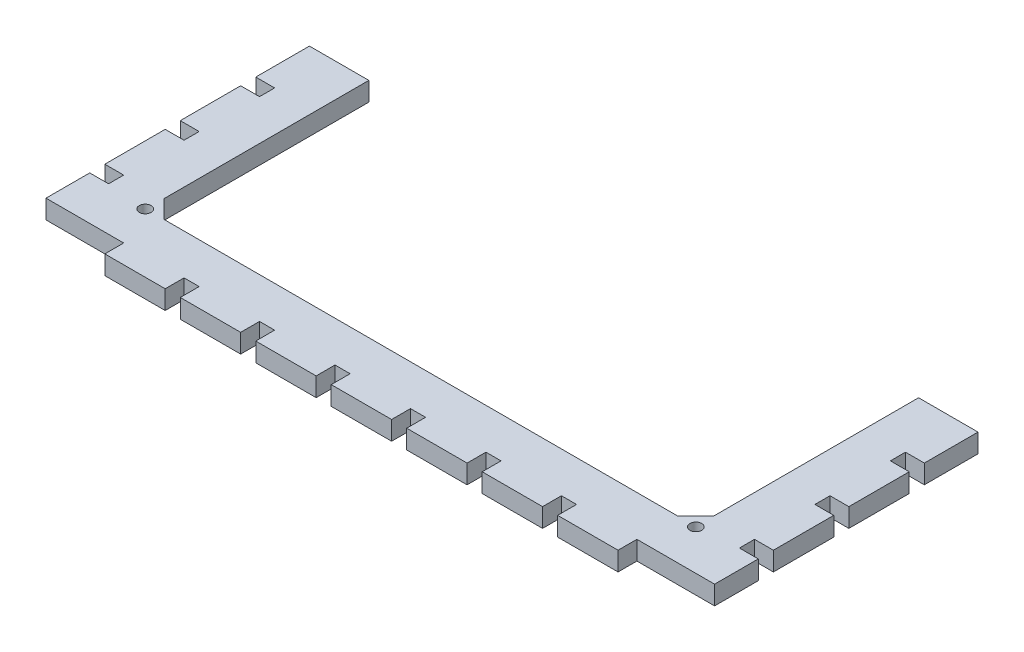
SolidWorks part; units mm, degrees
ref_plane "Front Plane" through (0, 0, 0) normal (0, 0, 1) x (1, 0, 0)
ref_plane "Top Plane" through (0, 0, 0) normal (0, 1, 0) x (1, 0, 0)
ref_plane "Right Plane" through (0, 0, 0) normal (1, 0, 0) x (0, 0, -1)
sketch "Sketch1" plane through (0, 0, 0) normal (0, 1, 0) x (1, 0, 0)
  line L48 (32.1429, 0) -> (32.1429, 6.35)
  line L49 (0, 0) -> (32.1429, 0)
  line L50 (0, 0) -> (0, 6.35)
  line L51 (0, 6.35) -> (32.1429, 6.35)
  line L52 (32.1429, 0) -> (32.1429, 6.35)
  line L53 (0, 0) -> (6.35, 0)
  line L54 (0, 0) -> (0, 32.1429)
  line L55 (0, 32.1429) -> (6.35, 32.1429)
  line L56 (6.35, 0) -> (6.35, 32.1429)
  line L57 (32.1429, 0) -> (64.2857, 0)
  line L58 (64.2857, 0) -> (64.2857, 6.35)
  line L59 (32.1429, 6.35) -> (64.2857, 6.35)
  line L60 (64.2857, 0) -> (64.2857, 6.35)
  line L61 (64.2857, 0) -> (96.4286, 0)
  line L62 (96.4286, 0) -> (96.4286, 6.35)
  line L63 (64.2857, 6.35) -> (96.4286, 6.35)
  line L64 (96.4286, 0) -> (96.4286, 6.35)
  line L65 (96.4286, 0) -> (128.5714, 0)
  line L66 (128.5714, 0) -> (128.5714, 6.35)
  line L67 (96.4286, 6.35) -> (128.5714, 6.35)
  line L72 (128.5714, 0) -> (128.5714, 6.35)
  line L73 (128.5714, 0) -> (160.7143, 0)
  line L74 (160.7143, 0) -> (160.7143, 6.35)
  line L75 (128.5714, 6.35) -> (160.7143, 6.35)
  line L76 (160.7143, 0) -> (160.7143, 6.35)
  line L77 (160.7143, 0) -> (192.8571, 0)
  line L78 (192.8571, 0) -> (192.8571, 6.35)
  line L79 (160.7143, 6.35) -> (192.8571, 6.35)
  line L80 (192.8571, 0) -> (192.8571, 6.35)
  line L81 (192.8571, 0) -> (225, 0)
  line L82 (225, 0) -> (225, 6.35)
  line L83 (192.8571, 6.35) -> (225, 6.35)
  line L84 (0, 32.1429) -> (0, 64.2857)
  line L85 (0, 32.1429) -> (6.35, 32.1429)
  line L86 (6.35, 32.1429) -> (6.35, 64.2857)
  line L87 (0, 64.2857) -> (6.35, 64.2857)
  line L88 (0, 64.2857) -> (0, 96.4286)
  line L89 (0, 64.2857) -> (6.35, 64.2857)
  line L90 (6.35, 64.2857) -> (6.35, 96.4286)
  line L91 (0, 96.4286) -> (6.35, 96.4286)
  line L98 (0, 96.4286) -> (0, 128.5714)
  line L99 (0, 96.4286) -> (6.35, 96.4286)
  line L100 (6.35, 96.4286) -> (6.35, 128.5714)
  line L101 (0, 128.5714) -> (6.35, 128.5714)
  line L102 (0, 128.5714) -> (0, 160.7143)
  line L103 (0, 128.5714) -> (6.35, 128.5714)
  line L104 (6.35, 128.5714) -> (6.35, 160.7143)
  line L105 (0, 160.7143) -> (6.35, 160.7143)
  line L106 (0, 160.7143) -> (0, 192.8571)
  line L107 (0, 160.7143) -> (6.35, 160.7143)
  line L108 (6.35, 160.7143) -> (6.35, 192.8571)
  line L109 (0, 192.8571) -> (6.35, 192.8571)
  line L110 (0, 192.8571) -> (0, 225)
  line L111 (0, 192.8571) -> (6.35, 192.8571)
  line L112 (6.35, 192.8571) -> (6.35, 225)
  line L113 (0, 225) -> (6.35, 225)
  line L114 (112.5, 0) -> (112.5, 671.069) construction
  line L115 (-187.856, 112.5) -> (254.8092, 112.5) construction
  line L116 (225, 32.1429) -> (218.65, 32.1429)
  line L117 (218.65, 0) -> (218.65, 32.1429)
  line L118 (225, 0) -> (218.65, 0)
  line L119 (225, 0) -> (225, 32.1429)
  line L120 (225, 192.8571) -> (218.65, 192.8571)
  line L121 (218.65, 192.8571) -> (218.65, 225)
  line L122 (225, 225) -> (218.65, 225)
  line L123 (225, 192.8571) -> (225, 225)
  line L124 (225, 160.7143) -> (218.65, 160.7143)
  line L125 (218.65, 160.7143) -> (218.65, 192.8571)
  line L126 (225, 192.8571) -> (218.65, 192.8571)
  line L127 (225, 160.7143) -> (225, 192.8571)
  line L128 (225, 32.1429) -> (218.65, 32.1429)
  line L129 (218.65, 32.1429) -> (218.65, 64.2857)
  line L130 (225, 64.2857) -> (218.65, 64.2857)
  line L131 (225, 32.1429) -> (225, 64.2857)
  line L132 (225, 128.5714) -> (218.65, 128.5714)
  line L133 (218.65, 128.5714) -> (218.65, 160.7143)
  line L134 (225, 160.7143) -> (218.65, 160.7143)
  line L135 (225, 128.5714) -> (225, 160.7143)
  line L136 (225, 96.4286) -> (218.65, 96.4286)
  line L137 (218.65, 96.4286) -> (218.65, 128.5714)
  line L138 (225, 128.5714) -> (218.65, 128.5714)
  line L139 (225, 96.4286) -> (225, 128.5714)
  line L140 (225, 64.2857) -> (218.65, 64.2857)
  line L141 (218.65, 64.2857) -> (218.65, 96.4286)
  line L142 (225, 96.4286) -> (218.65, 96.4286)
  line L143 (225, 64.2857) -> (225, 96.4286)
  line L144 (192.8571, 225) -> (225, 225)
  line L145 (225, 225) -> (225, 218.65)
  line L146 (192.8571, 218.65) -> (225, 218.65)
  line L147 (192.8571, 225) -> (192.8571, 218.65)
  line L148 (160.7143, 225) -> (192.8571, 225)
  line L149 (192.8571, 225) -> (192.8571, 218.65)
  line L150 (160.7143, 218.65) -> (192.8571, 218.65)
  line L151 (160.7143, 225) -> (160.7143, 218.65)
  line L152 (128.5714, 225) -> (160.7143, 225)
  line L153 (160.7143, 225) -> (160.7143, 218.65)
  line L154 (128.5714, 218.65) -> (160.7143, 218.65)
  line L155 (128.5714, 225) -> (128.5714, 218.65)
  line L156 (96.4286, 225) -> (128.5714, 225)
  line L157 (128.5714, 225) -> (128.5714, 218.65)
  line L158 (96.4286, 218.65) -> (128.5714, 218.65)
  line L159 (96.4286, 225) -> (96.4286, 218.65)
  line L160 (64.2857, 225) -> (96.4286, 225)
  line L161 (96.4286, 225) -> (96.4286, 218.65)
  line L162 (64.2857, 218.65) -> (96.4286, 218.65)
  line L163 (64.2857, 225) -> (64.2857, 218.65)
  line L164 (32.1429, 225) -> (64.2857, 225)
  line L165 (64.2857, 225) -> (64.2857, 218.65)
  line L166 (32.1429, 218.65) -> (64.2857, 218.65)
  line L167 (32.1429, 225) -> (32.1429, 218.65)
  line L168 (0, 218.65) -> (32.1429, 218.65)
  line L169 (32.1429, 225) -> (32.1429, 218.65)
  line L170 (0, 225) -> (32.1429, 225)
  line L171 (0, 225) -> (0, 218.65)
  point P56 (112.5, 6.35)
  point P58 (6.35, 112.5)
  dimension "D3" = 112.5
  dimension "D4" = 112.5
  dimension "D5" = 6.35
  dimension "D2" = 7
  dimension "D1" = 7
extrude "Boss-Extrude1" add sketch "Sketch1" along normal blind 6.35 contours L168 L112 L108 L104 L100 L90 L86 L56 L51 L59 L63 L67 L75 L79 L83 L117 L129 L141 L137 L133 L125 L121 L146 L150 L154 L158 L162 L166 | L164 L167 L166 L163 | L156 L159 L158 L155 | L148 L151 L150 L147 | L79 L74 L77 L78 | L67 L62 L65 L66 | L59 L48 L57 L58 region at (48.2143, 0, -3.175) region at (112.5, 0, -112.5) region at (112.5, 0, -3.175) region at (176.7857, 0, -3.175) region at (48.2143, 0, -221.825) region at (112.5, 0, -221.825) region at (176.7857, 0, -221.825)
sketch "Sketch2" plane through (0, 6.35, 0) normal (0, 1, 0) x (1, 0, 0)
  line L0 (218.65, 112.5) -> (6.35, 112.5) construction
  line L1 (218.65, 6.35) -> (218.65, 218.65) construction
  line L2 (6.35, 6.35) -> (6.35, 218.65) construction
  line L3 (160.7143, 225) -> (192.8571, 225) construction
  line L4 (6.35, 112.5) -> (218.65, 112.5)
  line L5 (6.35, 112.5) -> (6.35, 225)
  line L6 (6.35, 225) -> (218.65, 225)
  line L7 (218.65, 112.5) -> (218.65, 225)
extrude "Cut-Extrude1" cut sketch "Sketch2" against normal through all
sketch "Sketch3" plane through (0, 6.35, 0) normal (0, 1, 0) x (1, 0, 0)
  line L1 (6.35, 112.5) -> (218.65, 112.5)
  line L2 (6.35, 112.5) -> (6.35, 95)
  line L3 (6.35, 95) -> (218.65, 95)
  line L4 (218.65, 112.5) -> (218.65, 95)
  line L5 (218.65, 6.35) -> (218.65, 112.5) construction
  line L6 (192.8571, 6.35) -> (218.65, 6.35) construction
  dimension "D1" = 88.65
extrude "Cut-Extrude2" cut sketch "Sketch3" against normal up to surface (6.35 mm away) up to face at (112.5, 0, -17.2375)
sketch "Sketch4" plane through (0, 6.35, 0) normal (0, 1, 0) x (1, 0, 0)
  line L0 (6.35, 6.35) -> (6.35, 95) construction
  line L1 (6.35, 26.14) -> (0, 26.14)
  line L2 (6.35, 26.14) -> (6.35, 46.46)
  line L3 (6.35, 46.46) -> (0, 46.46)
  line L4 (0, 26.14) -> (0, 46.46)
  line L5 (6.35, 95) -> (0, 95)
  line L6 (6.35, 51.54) -> (0, 51.54)
  line L7 (6.35, 51.54) -> (6.35, 71.86)
  line L8 (6.35, 71.86) -> (0, 71.86)
  line L9 (0, 51.54) -> (0, 71.86)
  line L10 (6.35, 76.94) -> (0, 76.94)
  line L11 (6.35, 76.94) -> (6.35, 97.26)
  line L12 (6.35, 97.26) -> (0, 97.26)
  line L13 (0, 76.94) -> (0, 97.26)
  line L14 (6.35, 6.35) -> (0, 6.35)
  line L15 (6.35, 6.35) -> (6.35, 21.06)
  line L16 (6.35, 21.06) -> (0, 21.06)
  line L17 (0, 6.35) -> (0, 21.06)
  line L18 (112.5, 0) -> (112.5, 95) construction
  line L19 (96.4286, 0) -> (128.5714, 0) construction
  line L20 (6.35, 95) -> (218.65, 95) construction
  line L21 (225, 6.35) -> (225, 21.06)
  line L22 (218.65, 21.06) -> (225, 21.06)
  line L23 (218.65, 6.35) -> (218.65, 21.06)
  line L24 (218.65, 6.35) -> (225, 6.35)
  line L25 (225, 76.94) -> (225, 97.26)
  line L26 (218.65, 97.26) -> (225, 97.26)
  line L27 (218.65, 76.94) -> (218.65, 97.26)
  line L28 (218.65, 76.94) -> (225, 76.94)
  line L29 (225, 51.54) -> (225, 71.86)
  line L30 (218.65, 71.86) -> (225, 71.86)
  line L31 (218.65, 51.54) -> (218.65, 71.86)
  line L32 (218.65, 51.54) -> (225, 51.54)
  line L33 (218.65, 95) -> (225, 95)
  line L34 (225, 26.14) -> (225, 46.46)
  line L35 (218.65, 46.46) -> (225, 46.46)
  line L36 (218.65, 26.14) -> (218.65, 46.46)
  line L37 (218.65, 26.14) -> (225, 26.14)
  line L38 (225, 95) -> (218.65, 95)
  line L40 (225, 95) -> (218.65, 95)
  line L41 (225, 95) -> (225, 76.94)
  line L42 (225, 76.94) -> (218.65, 76.94)
  line L43 (218.65, 95) -> (218.65, 76.94)
  line M18 (6.35, 95) -> (6.35, 6.35)
  dimension "D1" = 20.32
  dimension "D2" = 5.08
  dimension "D3" = 5.08
  dimension "D4" = 5.08
  dimension "D5" = 14.71
  dimension "D6" = 6.35
extrude "Boss-Extrude2" add sketch "Sketch4" against normal up to surface (6.35 mm away) contours L13 L10 L5 M18 | L9 L6 L8 M18 | L4 L1 L3 M18 | L17 L14 L16 M18 | L41 L40 L43 L42 | L29 L30 L31 L32 | L34 L35 L36 L37 | L21 L22 L23 L24 region at (3.175, 6.35, -85.97) region at (3.175, 6.35, -61.7) region at (3.175, 6.35, -36.3) region at (3.175, 6.35, -13.705) up to face at (112.5, 0, -15.05)
sketch "Sketch5" plane through (0, 0, 0) normal (0, -1, 0) x (1, 0, 0)
  line L0 (225, -95) -> (0, -95) construction
  line L1 (205, -95) -> (20, -95)
  line L2 (205, -95) -> (205, -20)
  line L3 (205, -20) -> (20, -20)
  line L4 (20, -95) -> (20, -20)
  line L5 (112.5, 0) -> (112.5, -133.1244) construction
  line L7 (96.4286, 0) -> (128.5714, 0) construction
  line L8 (0, -46.46) -> (0, -26.14) construction
  line L10 (32.1429, 0) -> (64.2857, 0) construction
  point P9 (112.5, 0)
  point P11 (112.5, -95)
  dimension "D1" = 20
  dimension "D2" = 20
extrude "Cut-Extrude3" cut sketch "Sketch5" against normal through all
sketch "Sketch6" plane through (0, 0, 0) normal (0, -1, 0) x (1, 0, 0)
  line L0 (0, -21.06) -> (0, -6.35) construction
  line L1 (225, -6.35) -> (0, -6.35)
  line L2 (225, -6.35) -> (225, 0)
  line L3 (225, 0) -> (0, 0)
  line L4 (0, -6.35) -> (0, 0)
  line L5 (32.1429, 0) -> (64.2857, 0) construction
extrude "Boss-Extrude3" add sketch "Sketch6" against normal up to surface (6.35 mm away) up to face at (112.5, 6.35, -37.4273)
sketch "Sketch7" plane through (0, 0, 0) normal (0, -1, 0) x (1, 0, 0)
  line L0 (0, 0) -> (225, 0) construction
  line L1 (178.54, -6.35) -> (198.86, -6.35)
  line L2 (178.54, -6.35) -> (178.54, 0)
  line L3 (178.54, 0) -> (198.86, 0)
  line L4 (198.86, -6.35) -> (198.86, 0)
  line L5 (153.14, -6.35) -> (153.14, 0)
  line L6 (153.14, -6.35) -> (173.46, -6.35)
  line L7 (173.46, -6.35) -> (173.46, 0)
  line L8 (153.14, 0) -> (173.46, 0)
  line L9 (127.74, -6.35) -> (127.74, 0)
  line L10 (127.74, -6.35) -> (148.06, -6.35)
  line L11 (148.06, -6.35) -> (148.06, 0)
  line L12 (127.74, 0) -> (148.06, 0)
  line L13 (102.34, -6.35) -> (102.34, 0)
  line L14 (102.34, -6.35) -> (122.66, -6.35)
  line L15 (122.66, -6.35) -> (122.66, 0)
  line L16 (102.34, 0) -> (122.66, 0)
  line L17 (76.94, -6.35) -> (76.94, 0)
  line L18 (76.94, -6.35) -> (97.26, -6.35)
  line L19 (97.26, -6.35) -> (97.26, 0)
  line L20 (76.94, 0) -> (97.26, 0)
  line L21 (51.54, -6.35) -> (51.54, 0)
  line L22 (51.54, -6.35) -> (71.86, -6.35)
  line L23 (71.86, -6.35) -> (71.86, 0)
  line L24 (51.54, 0) -> (71.86, 0)
  line L25 (26.14, -6.35) -> (26.14, 0)
  line L26 (26.14, -6.35) -> (46.46, -6.35)
  line L27 (46.46, -6.35) -> (46.46, 0)
  line L28 (26.14, 0) -> (46.46, 0)
  line L30 (178.54, -6.35) -> (173.46, -6.35)
  line L31 (178.54, -6.35) -> (178.54, 0)
  line L32 (178.54, 0) -> (173.46, 0)
  line L33 (173.46, -6.35) -> (173.46, 0)
  line L34 (153.14, -6.35) -> (148.06, -6.35)
  line L35 (153.14, -6.35) -> (153.14, 0)
  line L36 (153.14, 0) -> (148.06, 0)
  line L37 (148.06, -6.35) -> (148.06, 0)
  line L38 (127.74, -6.35) -> (122.66, -6.35)
  line L39 (127.74, -6.35) -> (127.74, 0)
  line L40 (127.74, 0) -> (122.66, 0)
  line L41 (122.66, -6.35) -> (122.66, 0)
  line L42 (102.34, -6.35) -> (97.26, -6.35)
  line L43 (102.34, -6.35) -> (102.34, 0)
  line L44 (102.34, 0) -> (97.26, 0)
  line L45 (97.26, -6.35) -> (97.26, 0)
  line L46 (76.94, -6.35) -> (71.86, -6.35)
  line L47 (76.94, -6.35) -> (76.94, 0)
  line L48 (76.94, 0) -> (71.86, 0)
  line L49 (71.86, -6.35) -> (71.86, 0)
  line L50 (51.54, -6.35) -> (46.46, -6.35)
  line L51 (51.54, -6.35) -> (51.54, 0)
  line L52 (51.54, 0) -> (46.46, 0)
  line L53 (46.46, -6.35) -> (46.46, 0)
  line L54 (198.86, -6.35) -> (225, -6.35)
  line L55 (198.86, -6.35) -> (198.86, 0)
  line L56 (198.86, 0) -> (225, 0)
  line L57 (225, -6.35) -> (225, 0)
  line L58 (26.14, -6.35) -> (0, -6.35)
  line L59 (26.14, -6.35) -> (26.14, 0)
  line L60 (26.14, 0) -> (0, 0)
  line L61 (0, -6.35) -> (0, 0)
  point P31 (112.5, 0)
  point P32 (112.5, 0)
  point P34 (137.9, 0)
  line M27 (225, 0) -> (0, 0)
  dimension "D2" = 25.4
  dimension "D3" = 5.08
  dimension "D4" = 6.35
  dimension "D1" = 7
extrude "Cut-Extrude4" cut sketch "Sketch7" against normal through all contours L30 L2 L7 M27 | L34 L5 L11 M27 | L38 L9 L15 M27 | L42 L13 L19 M27 | L46 L17 L23 M27 | L50 L21 L27 M27 | L55 L54 L57 L56 | L59 L58 L61 L60 region at (176, 0, -3.175) region at (150.6, 0, -3.175) region at (125.2, 0, -3.175) region at (99.8, 0, -3.175) region at (74.4, 0, -3.175) region at (49, 0, -3.175)
sketch "Sketch8" plane through (0, 0, 0) normal (0, -1, 0) x (1, 0, 0)
  line L0 (20, -26.0104) -> (26.0104, -20)
  line L1 (20, -20) -> (20, -95) construction
  line L2 (26.0104, -20) -> (20, -20)
  line L3 (20, -20) -> (20, -26.0104)
  line L4 (112.5, 0) -> (112.5, -20) construction
  line L5 (102.34, 0) -> (122.66, 0) construction
  line L6 (205, -20) -> (20, -20) construction
  line L7 (198.9896, -20) -> (205, -20)
  line L8 (205, -26.0104) -> (198.9896, -20)
  line L9 (205, -20) -> (205, -26.0104)
  dimension "D1" = 4.25
extrude "Boss-Extrude4" add sketch "Sketch8" against normal up to surface (6.35 mm away) contours L3 L0 L2 | L7 L9 L8 up to face at (112.5, 6.35, -28.2933)
sketch "Sketch9" plane through (0, 0, 0) normal (0, -1, 0) x (-1, 0, 0)
  line L0 (-225, 46.46) -> (-225, 26.14) construction
  line L2 (-198.86, 6.35) -> (-225, 6.35) construction
  line L3 (-112.5, 0) -> (-112.5, 20) construction
  line L4 (-102.34, 0) -> (-122.66, 0) construction
  line L5 (-198.9896, 20) -> (-26.0104, 20) construction
  circle A0 centre (-205.15, 19.88) radius 2
  circle A1 centre (-19.85, 19.88) radius 2
  dimension "D3" = 4
  dimension "D1" = 19.85
  dimension "D2" = 13.53
extrude "Cut-Extrude5" cut sketch "Sketch9" against normal through all
